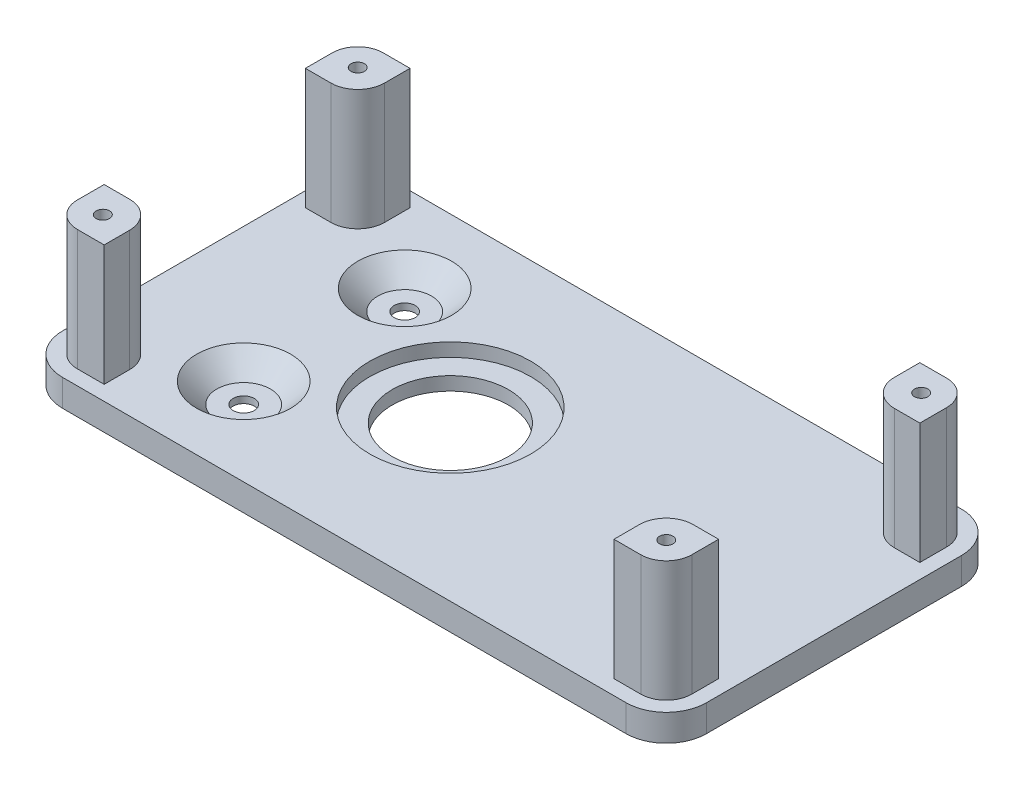
SolidWorks part; units mm, degrees
ref_plane "Front Plane" through (0, 0, 0) normal (0, 0, 1) x (1, 0, 0)
ref_plane "Top Plane" through (0, 0, 0) normal (0, 1, 0) x (1, 0, 0)
ref_plane "Right Plane" through (0, 0, 0) normal (1, 0, 0) x (0, 0, -1)
sketch "Sketch1" plane through (0, 0, 0) normal (0, 1, 0) x (1, 0, 0)
  line L1 (0, 0) -> (121.92, 0)
  line L2 (0, 0) -> (0, 63.5)
  line L3 (0, 63.5) -> (121.92, 63.5)
  line L4 (121.92, 0) -> (121.92, 63.5)
  dimension "D1" = 63.5
  dimension "D2" = 121.92
extrude "Boss-Extrude1" add sketch "Sketch1" along normal blind 5.08
fillet "Fillet1" radius 7.62 4 edges at (0, 2.54, 0) (0, 2.54, -63.5) (121.92, 2.54, -63.5) (121.92, 2.54, 0)
sketch "Sketch2" plane through (0, 5.08, 0) normal (0, 1, 0) x (1, 0, 0)
  line L0 (0, 55.88) -> (0, 7.62) construction
  line L1 (2.794, 60.706) -> (12.7, 60.706)
  line L2 (2.794, 60.706) -> (2.794, 50.8)
  line L3 (2.794, 50.8) -> (12.7, 50.8)
  line L4 (12.7, 60.706) -> (12.7, 50.8)
  line L5 (114.3, 63.5) -> (7.62, 63.5) construction
  line L6 (60.96, 63.5) -> (60.96, 0) construction
  line L7 (7.62, 0) -> (114.3, 0) construction
  line L8 (121.92, 31.75) -> (0, 31.75) construction
  line L9 (121.92, 7.62) -> (121.92, 55.88) construction
  line L10 (109.22, 60.706) -> (109.22, 50.8)
  line L11 (119.126, 50.8) -> (109.22, 50.8)
  line L12 (119.126, 60.706) -> (119.126, 50.8)
  line L13 (119.126, 60.706) -> (109.22, 60.706)
  line L14 (119.126, 2.794) -> (109.22, 2.794)
  line L15 (119.126, 2.794) -> (119.126, 12.7)
  line L16 (119.126, 12.7) -> (109.22, 12.7)
  line L17 (109.22, 2.794) -> (109.22, 12.7)
  line L18 (12.7, 2.794) -> (12.7, 12.7)
  line L19 (2.794, 12.7) -> (12.7, 12.7)
  line L20 (2.794, 2.794) -> (2.794, 12.7)
  line L21 (2.794, 2.794) -> (12.7, 2.794)
  dimension "D1" = 2.794
  dimension "D2" = 2.794
  dimension "D3" = 9.906
  dimension "D4" = 9.906
extrude "Boss-Extrude2" add sketch "Sketch2" along normal blind 22.86
fillet "Fillet2" radius 4.826 4 edges at (2.794, 16.51, -60.706) (119.126, 16.51, -60.706) (119.126, 16.51, -2.794) (2.794, 16.51, -2.794)
fillet "Fillet3" radius 5.08 4 edges at (12.7, 16.51, -12.7) (109.22, 16.51, -12.7) (109.22, 16.51, -50.8) (12.7, 16.51, -50.8)
sketch "Sketch3" plane through (0, 27.94, 0) normal (0, 1, 0) x (1, 0, 0)
  circle A0 centre (7.62, 55.88) radius 1.27
  circle A1 centre (114.3, 55.88) radius 1.27
  circle A2 centre (114.3, 7.62) radius 1.27
  circle A3 centre (7.62, 7.62) radius 1.27
  dimension "D1" = 2.54
  dimension "D2" = 2.54
  dimension "D3" = 2.54
  dimension "D4" = 2.54
extrude "Cut-Extrude1" cut sketch "Sketch3" against normal blind 22.86
sketch "Sketch5" plane through (0, 0, 0) normal (0, -1, 0) x (1, 0, 0)
  circle A0 centre (49.276, -31.75) radius 10.9982
  dimension "D1" = 24.13
  dimension "D2" = 21.9964
  dimension "D3" = 49.276
extrude "Cut-Extrude2" cut sketch "Sketch5" against normal up to next
sketch "Sketch6" plane through (0, 0, 0) normal (0, -1, 0) x (1, 0, 0)
  line L0 (0, -55.88) -> (0, -7.62) construction
  circle A0 centre (25.4, -16.51) radius 1.9939
  circle A1 centre (25.4, -46.99) radius 1.9939
  point P6 (0, -31.75)
  dimension "D1" = 3.9878
  dimension "D2" = 3.9878
  dimension "D3" = 25.4
  dimension "D4" = 15.24
  dimension "D5" = 15.24
extrude "Cut-Extrude3" cut sketch "Sketch6" against normal up to next
sketch "Sketch7" plane through (0, 5.08, 0) normal (0, 1, 0) x (1, 0, 0)
  circle A0 centre (25.4, 46.99) radius 5.08
  circle A1 centre (25.4, 16.51) radius 5.08
  dimension "D1" = 10.16
  dimension "D2" = 10.16
extrude "Cut-Extrude4" cut sketch "Sketch7" against normal blind 3.81
chamfer "Chamfer1" distance 3.81 angle 45 2 edges at (25.4, 5.08, -11.43) (25.4, 5.08, -41.91)
sketch "Sketch8" plane through (0, 5.08, 0) normal (0, 1, 0) x (1, 0, 0)
  circle A0 centre (49.276, 31.75) radius 15.24
  dimension "D1" = 30.48
extrude "Cut-Extrude5" cut sketch "Sketch8" against normal blind 2.54
